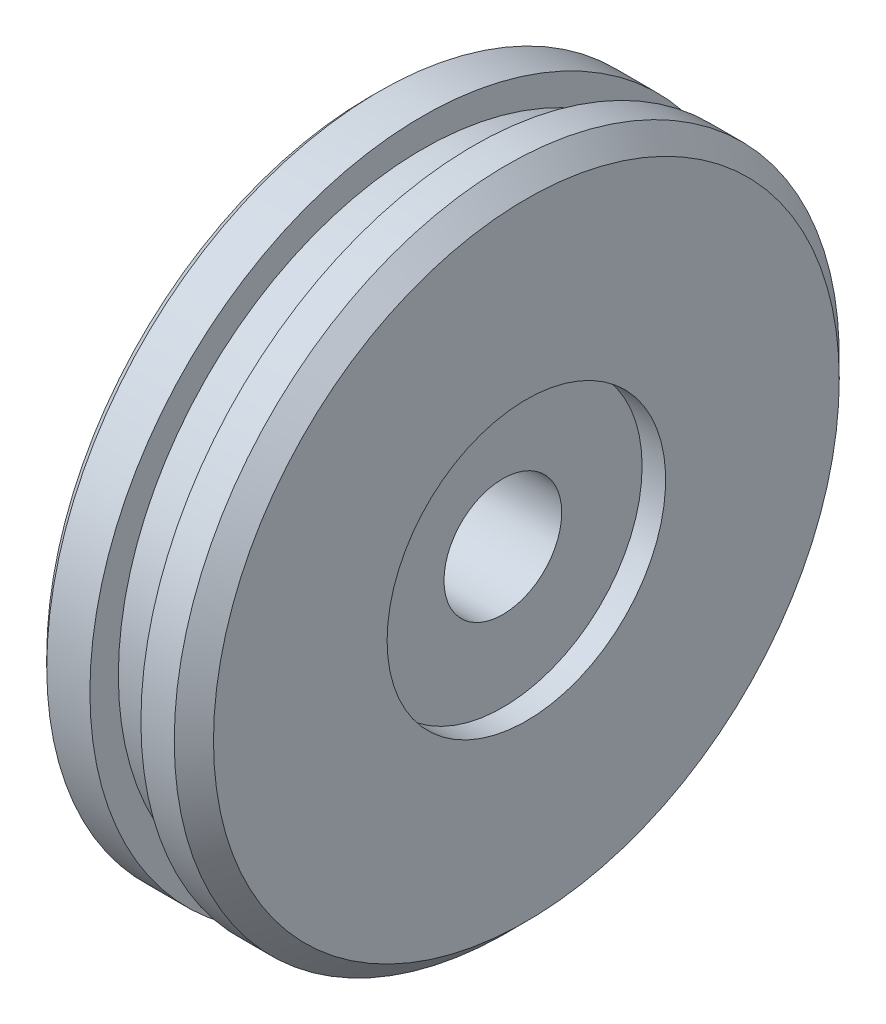
SolidWorks part; units mm, degrees
ref_plane "Front Plane" through (0, 0, 0) normal (0, 0, 1) x (1, 0, 0)
ref_plane "Top Plane" through (0, 0, 0) normal (0, 1, 0) x (1, 0, 0)
ref_plane "Right Plane" through (0, 0, 0) normal (1, 0, 0) x (0, 0, -1)
ref_plane "Plane1" through (0, 0, -52) normal (0, 0, 1) x (1, 0, 0)
sketch "Sketch1" plane through (0, 0, -52) normal (0, 0, 1) x (1, 0, 0)
  line L0 (72.2, -65) -> (90.2, -65) construction
  line L1 (77.2, -65) -> (85.2, -65)
  line L2 (85.2, -65) -> (85.2, -49.05)
  line L3 (85.2, -49.05) -> (84.2, -48.05)
  line L4 (84.2, -48.05) -> (77.7, -48.05)
  line L5 (77.7, -48.05) -> (77.2, -48.55)
  line L6 (77.2, -48.55) -> (77.2, -65)
revolve "Revolve1" add sketch "Sketch1" angle 360 about L0
sketch "Sketch2" plane through (0, 0, -52) normal (0, 0, 1) x (1, 0, 0)
  line L0 (74.9, -65) -> (87.5, -65) construction
  line L1 (79.9, -49.5) -> (82.5, -49.5)
  line L2 (82.5, -49.5) -> (82.5, -47.05)
  line L3 (82.5, -47.05) -> (79.9, -47.05)
  line L4 (79.9, -47.05) -> (79.9, -49.5)
revolve "Revolve2" add sketch "Sketch2" angle 360 about L0
combine bodies "Combine1" operation type subtract main body 101 bodies to subtract 102
sketch "Sketch3" plane through (0, 0, 0) normal (0, 0, 1) x (1, 0, 0)
  line L1 (76.7, -76.5) -> (79, -76.5)
  line L2 (76.7, -76.5) -> (76.7, -53.5)
  line L3 (76.7, -53.5) -> (79, -53.5)
  line L4 (79, -76.5) -> (79, -53.5)
extrude "Boss-Extrude1" add sketch "Sketch3" along normal blind 6.6 from offset 55.3 separate body offset against normal yes
combine bodies "Combine2" operation type subtract main body 103 bodies to subtract 104
sketch "Sketch4" plane through (0, 0, 0) normal (0, 0, 1) x (1, 0, 0)
  line L1 (76.7, -68.3) -> (79, -68.3)
  line L2 (76.7, -68.3) -> (76.7, -61.7)
  line L3 (76.7, -61.7) -> (79, -61.7)
  line L4 (79, -68.3) -> (79, -61.7)
extrude "Boss-Extrude2" add sketch "Sketch4" along normal blind 23 from offset 63.5 separate body offset against normal yes
combine bodies "Combine3" operation type subtract main body 105 bodies to subtract 106
sketch "Sketch5" plane through (0, 0, 0) normal (1, 0, 0) x (0, 0, -1)
  circle A0 centre (52, -65) radius 4.6
extrude "Boss-Extrude3" add sketch "Sketch5" along normal blind 2.3 from offset 76.7 separate body
combine bodies "Combine4" operation type subtract main body 107 bodies to subtract 108
sketch "Sketch6" plane through (0, 0, 0) normal (1, 0, 0) x (0, 0, -1)
  circle A0 centre (52, -65) radius 7.1
extrude "Boss-Extrude4" add sketch "Sketch6" along normal blind 1.7 from offset 84 separate body
combine bodies "Combine5" operation type subtract main body 109 bodies to subtract 110
sketch "Sketch7" plane through (0, 0, 0) normal (1, 0, 0) x (0, 0, -1)
  circle A0 centre (52, -65) radius 3
extrude "Boss-Extrude5" add sketch "Sketch7" along normal blind 5.2 from offset 78.9 separate body
combine bodies "Combine6" operation type subtract main body 111 bodies to subtract 112
sketch "Sketch8" plane through (0, 0, 0) normal (0, 0, 1) x (1, 0, 0)
  line L1 (78.9, -59.5) -> (83, -59.5)
  line L2 (78.9, -59.5) -> (78.9, -57.4)
  line L3 (78.9, -57.4) -> (83, -57.4)
  line L4 (83, -59.5) -> (83, -57.4)
extrude "Boss-Extrude6" add sketch "Sketch8" along normal blind 1.8 from offset 52.9 separate body offset against normal yes
combine bodies "Combine7" operation type subtract main body 113 bodies to subtract 114
sketch "Sketch9" plane through (0, 0, 0) normal (0, 0, 1) x (1, 0, 0)
  line L1 (78.9, -65.9) -> (83, -65.9)
  line L2 (78.9, -65.9) -> (78.9, -64.1)
  line L3 (78.9, -64.1) -> (83, -64.1)
  line L4 (83, -65.9) -> (83, -64.1)
extrude "Boss-Extrude7" add sketch "Sketch9" along normal blind 2.1 from offset 46.5 separate body offset against normal yes
combine bodies "Combine8" operation type subtract main body 115 bodies to subtract 116
sketch "Sketch10" plane through (0, 0, 0) normal (0, 0, 1) x (1, 0, 0)
  line L1 (78.9, -72.6) -> (83, -72.6)
  line L2 (78.9, -72.6) -> (78.9, -70.5)
  line L3 (78.9, -70.5) -> (83, -70.5)
  line L4 (83, -72.6) -> (83, -70.5)
extrude "Boss-Extrude8" add sketch "Sketch10" along normal blind 1.8 from offset 52.9 separate body offset against normal yes
combine bodies "Combine9" operation type subtract main body 117 bodies to subtract 118
sketch "Sketch11" plane through (0, 0, 0) normal (0, 0, 1) x (1, 0, 0)
  line L1 (78.9, -65.9) -> (83, -65.9)
  line L2 (78.9, -65.9) -> (78.9, -64.1)
  line L3 (78.9, -64.1) -> (83, -64.1)
  line L4 (83, -65.9) -> (83, -64.1)
extrude "Boss-Extrude9" add sketch "Sketch11" along normal blind 2.1 from offset 59.6 separate body offset against normal yes
combine bodies "Combine10" operation type subtract main body 119 bodies to subtract 120
sketch "Sketch12" plane through (0, 0, 0) normal (0, 0, 1) x (1, 0, 0)
  line L1 (78.9, -57.4) -> (84.2, -57.4)
  line L2 (78.9, -57.4) -> (78.9, -55)
  line L3 (78.9, -55) -> (84.2, -55)
  line L4 (84.2, -57.4) -> (84.2, -55)
extrude "Boss-Extrude10" add sketch "Sketch12" along normal blind 1.8 from offset 52.9 separate body offset against normal yes
combine bodies "Combine11" operation type subtract main body 121 bodies to subtract 122
sketch "Sketch13" plane through (0, 0, 0) normal (0, 0, 1) x (1, 0, 0)
  line L1 (78.9, -65.9) -> (84.2, -65.9)
  line L2 (78.9, -65.9) -> (78.9, -64.1)
  line L3 (78.9, -64.1) -> (84.2, -64.1)
  line L4 (84.2, -65.9) -> (84.2, -64.1)
extrude "Boss-Extrude11" add sketch "Sketch13" along normal blind 2.4 from offset 44.4 separate body offset against normal yes
combine bodies "Combine12" operation type subtract main body 123 bodies to subtract 124
sketch "Sketch14" plane through (0, 0, 0) normal (0, 0, 1) x (1, 0, 0)
  line L1 (78.9, -75) -> (84.2, -75)
  line L2 (78.9, -75) -> (78.9, -72.6)
  line L3 (78.9, -72.6) -> (84.2, -72.6)
  line L4 (84.2, -75) -> (84.2, -72.6)
extrude "Boss-Extrude12" add sketch "Sketch14" along normal blind 1.8 from offset 52.9 separate body offset against normal yes
combine bodies "Combine13" operation type subtract main body 125 bodies to subtract 126
sketch "Sketch15" plane through (0, 0, 0) normal (0, 0, 1) x (1, 0, 0)
  line L1 (78.9, -65.9) -> (84.2, -65.9)
  line L2 (78.9, -65.9) -> (78.9, -64.1)
  line L3 (78.9, -64.1) -> (84.2, -64.1)
  line L4 (84.2, -65.9) -> (84.2, -64.1)
extrude "Boss-Extrude13" add sketch "Sketch15" along normal blind 2.4 from offset 62 separate body offset against normal yes
combine bodies "Combine14" operation type subtract main body 127 bodies to subtract 128
